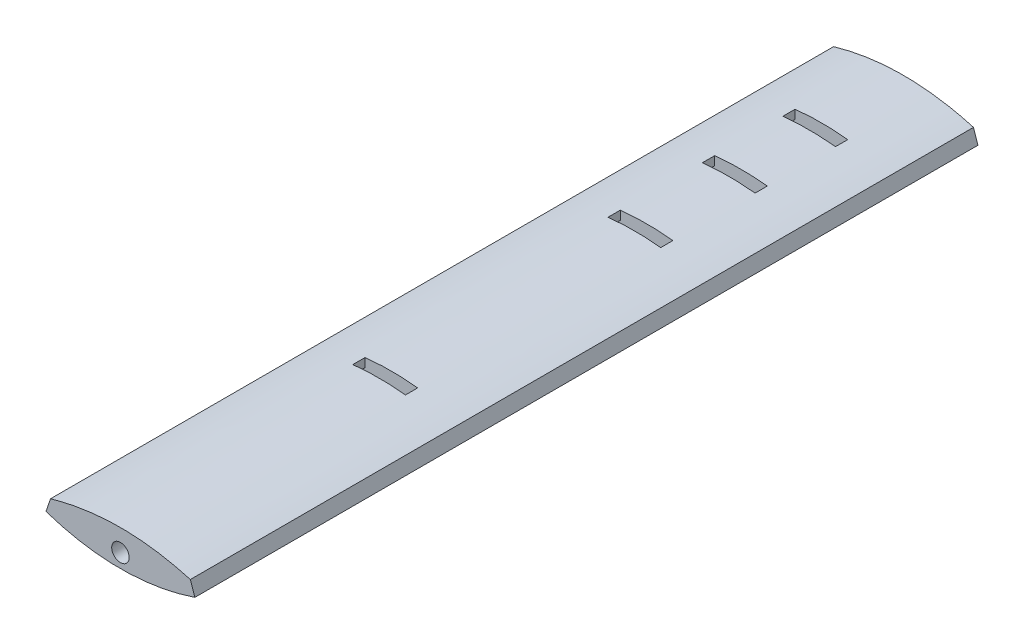
SolidWorks part; units mm, degrees
ref_plane "Front Plane" through (0, 0, 0) normal (0, 0, 1) x (1, 0, 0)
ref_plane "Top Plane" through (0, 0, 0) normal (0, 1, 0) x (1, 0, 0)
ref_plane "Right Plane" through (0, 0, 0) normal (1, 0, 0) x (0, 0, -1)
sketch "Sketch1" plane through (0, 0, 0) normal (0, 0, 1) x (-1, 0, 0)
  line L0 (-10.6452, 31.2359) -> (-10, 29.3428)
  line L1 (-10, 29.3428) -> (0, 27.9) construction
  line L3 (0, 27.9) -> (10, 29.3428) construction
  line L4 (10, 29.3428) -> (10.6452, 31.2359)
  circle A0 centre (0, 31) radius 2
  circle A2 centre (0, 31) radius 1.25
  arc A4 (10.6452, 31.2359) -> (-10.6452, 31.2359) centre (0, 0) ccw
  spline S0 degree 2 poles (-10, 29.3428) (0, 26.4572) (10, 29.3428) knots 0 0 0 1 1 1
sketch "Sketch2" plane through (0, 0, 0) normal (0, 0, 1) x (1, 0, 0)
  line L0 (-10, -29.3428) -> (-10.6452, -31.2359) construction
  line L1 (-10, -29.3428) -> (-10.6452, -31.2359)
  line L2 (10.6452, -31.2359) -> (10, -29.3428) construction
  line L3 (10.6452, -31.2359) -> (10, -29.3428)
  arc A0 (-10.6452, -31.2359) -> (10.6452, -31.2359) centre (0, 0) ccw construction
  circle A1 centre (0, -31) radius 1.25 construction
  arc A3 (-10.6452, -31.2359) -> (10.6452, -31.2359) centre (0, 0) ccw
  circle A4 centre (0, -31) radius 1.25
  parabola Q0 (10, -29.3428) -> (-10, -29.3428) focus (0, -45.2274) apex (0, -27.9) construction
  parabola Q1 (10, -29.3428) -> (-10, -29.3428) focus (0, -45.2274) apex (0, -27.9)
extrude "Boss-Extrude1" add sketch "Sketch2" along normal blind 1.5
sketch "Sketch3" plane through (0, 0, 0) normal (0, 0, -1) x (-1, 0, 0)
  line L0 (-10.6452, -31.2359) -> (-10, -29.3428) construction
  line L1 (10, -29.3428) -> (10.6452, -31.2359) construction
  line L2 (-10.6452, -31.2359) -> (-10, -29.3428)
  line L3 (10, -29.3428) -> (10.6452, -31.2359)
  line L4 (0, -31) -> (0, -27.9) construction
  arc A2 (-10.6452, -31.2359) -> (10.6452, -31.2359) centre (0, 0) ccw construction
  arc A3 (-10.6452, -31.2359) -> (-7.7645, -32.0736) centre (0, 0) ccw
  arc A4 (7.7645, -32.0736) -> (10.6452, -31.2359) centre (0, 0) ccw
  parabola Q0 (-10, -29.3428) -> (10, -29.3428) focus (0, -45.2274) apex (0, -27.9) construction
  parabola Q1 (-10, -29.3428) -> (10, -29.3428) focus (0, -45.2274) apex (0, -27.9)
  spline S0 degree 2 poles (-7.7645, -32.0736) (0, -24.9991) (7.7645, -32.0736) knots 0 0 0 1 1 1
  point P12 (-7.7645, -32.0736)
  point P13 (7.7645, -32.0736)
  dimension "D1" = 3
  dimension "D2" = 3
extrude "Boss-Extrude2" add sketch "Sketch3" along normal blind 113.5
ref_plane "Plane1" through (0, 0, -110) normal (0, 0, 1) x (1, 0, 0)
ref_plane "Plane2" through (0, 0, -37) normal (0, 0, 1) x (1, 0, 0)
sketch "Sketch5" plane through (0, 0, -110) normal (0, 0, 1) x (1, 0, 0)
  line L0 (-10, -29.3428) -> (-10.6452, -31.2359) construction
  line L1 (10.6452, -31.2359) -> (10, -29.3428) construction
  line L2 (-10, -29.3428) -> (-10.6452, -31.2359)
  line L3 (10.6452, -31.2359) -> (10, -29.3428)
  arc A0 (-10.6452, -31.2359) -> (10.6452, -31.2359) centre (0, 0) ccw construction
  circle A1 centre (0, -31) radius 1.25 construction
  arc A2 (-10.6452, -31.2359) -> (10.6452, -31.2359) centre (0, 0) ccw
  circle A3 centre (0, -31) radius 1.25
  parabola Q0 (10, -29.3428) -> (-10, -29.3428) focus (0, -45.2274) apex (0, -27.9) construction
  parabola Q1 (10, -29.3428) -> (-10, -29.3428) focus (0, -45.2274) apex (0, -27.9)
extrude "Boss-Extrude4" add sketch "Sketch5" against normal up to vertex (3.5 mm away)
sketch "Sketch6" plane through (0, 0, -37) normal (0, 0, 1) x (1, 0, 0)
  line L2 (-10, -29.3428) -> (-10.6452, -31.2359)
  line L3 (10.6452, -31.2359) -> (10, -29.3428)
  line L4 (-10, -29.3428) -> (-10.6452, -31.2359)
  line L5 (10.6452, -31.2359) -> (10, -29.3428)
  circle A0 centre (0, -31) radius 1.25 construction
  arc A1 (-10.6452, -31.2359) -> (10.6452, -31.2359) centre (0, 0) ccw
  arc A2 (-10.6452, -31.2359) -> (10.6452, -31.2359) centre (0, 0) ccw
  circle A3 centre (0, -31) radius 1.25
  parabola Q1 (10, -29.3428) -> (-10, -29.3428) focus (0, -45.2274) apex (0, -27.9)
  parabola Q2 (10, -29.3428) -> (-10, -29.3428) focus (0, -45.2274) apex (0, -27.9)
  dimension "D1" = 0
extrude "Boss-Extrude5" add sketch "Sketch6" along normal blind 1.5
ref_plane "Plane4" through (0, 0, -73.5) normal (0, 0, 1) x (1, 0, 0)
sketch "Sketch8" plane through (0, 0, -73.5) normal (0, 0, 1) x (1, 0, 0)
  line L2 (-10, -29.3428) -> (-10.6452, -31.2359)
  line L3 (10.6452, -31.2359) -> (10, -29.3428)
  line L4 (-10, -29.3428) -> (-10.6452, -31.2359)
  line L5 (10.6452, -31.2359) -> (10, -29.3428)
  circle A0 centre (0, -31) radius 1.25 construction
  arc A1 (-10.6452, -31.2359) -> (10.6452, -31.2359) centre (0, 0) ccw
  arc A2 (-10.6452, -31.2359) -> (10.6452, -31.2359) centre (0, 0) ccw
  circle A3 centre (0, -31) radius 1.25
  parabola Q1 (10, -29.3428) -> (-10, -29.3428) focus (0, -45.2274) apex (0, -27.9)
  parabola Q2 (10, -29.3428) -> (-10, -29.3428) focus (0, -45.2274) apex (0, -27.9)
  dimension "D1" = 0
extrude "Boss-Extrude7" add sketch "Sketch8" along normal blind 1.5
ref_plane "Plane5" through (0, 0, -76.75) normal (0, 0, 1) x (1, 0, 0)
sketch "Sketch9" plane through (0, 0, -76.75) normal (0, 0, 1) x (1, 0, 0)
  line L2 (-10, -29.3428) -> (-10.6452, -31.2359)
  line L3 (10.6452, -31.2359) -> (10, -29.3428)
  line L4 (-10, -29.3428) -> (-10.6452, -31.2359)
  line L5 (10.6452, -31.2359) -> (10, -29.3428)
  circle A0 centre (0, -31) radius 1.25 construction
  arc A1 (-10.6452, -31.2359) -> (10.6452, -31.2359) centre (0, 0) ccw
  arc A2 (-10.6452, -31.2359) -> (10.6452, -31.2359) centre (0, 0) ccw
  circle A3 centre (0, -31) radius 1.25
  parabola Q1 (10, -29.3428) -> (-10, -29.3428) focus (0, -45.2274) apex (0, -27.9)
  parabola Q2 (10, -29.3428) -> (-10, -29.3428) focus (0, -45.2274) apex (0, -27.9)
  dimension "D1" = 0
extrude "Boss-Extrude8" add sketch "Sketch9" along normal blind 1.5
ref_plane "Plane6" through (0, 0, -40.25) normal (0, 0, 1) x (1, 0, 0)
sketch "Sketch10" plane through (0, 0, -40.25) normal (0, 0, 1) x (1, 0, 0)
  line L2 (-10, -29.3428) -> (-10.6452, -31.2359)
  line L3 (10.6452, -31.2359) -> (10, -29.3428)
  line L4 (-10, -29.3428) -> (-10.6452, -31.2359)
  line L5 (10.6452, -31.2359) -> (10, -29.3428)
  circle A0 centre (0, -31) radius 1.25 construction
  arc A1 (-10.6452, -31.2359) -> (10.6452, -31.2359) centre (0, 0) ccw
  arc A2 (-10.6452, -31.2359) -> (10.6452, -31.2359) centre (0, 0) ccw
  circle A3 centre (0, -31) radius 1.25
  parabola Q1 (10, -29.3428) -> (-10, -29.3428) focus (0, -45.2274) apex (0, -27.9)
  parabola Q2 (10, -29.3428) -> (-10, -29.3428) focus (0, -45.2274) apex (0, -27.9)
  dimension "D1" = 0
extrude "Boss-Extrude9" add sketch "Sketch10" along normal blind 1.5
ref_plane "Plane7" through (0, 0, -87) normal (0, 0, 1) x (1, 0, 0)
ref_plane "Plane8" through (0, 0, -98.5) normal (0, 0, 1) x (1, 0, 0)
ref_plane "Plane9" through (0, 0, -90.25) normal (0, 0, 1) x (1, 0, 0)
ref_plane "Plane10" through (0, 0, -101.75) normal (0, 0, 1) x (1, 0, 0)
sketch "Sketch12" plane through (0, 0, -101.75) normal (0, 0, 1) x (1, 0, 0)
  line L2 (-10, -29.3428) -> (-10.6452, -31.2359)
  line L3 (10.6452, -31.2359) -> (10, -29.3428)
  line L4 (-10, -29.3428) -> (-10.6452, -31.2359)
  line L5 (10.6452, -31.2359) -> (10, -29.3428)
  circle A0 centre (0, -31) radius 1.25 construction
  arc A1 (-10.6452, -31.2359) -> (10.6452, -31.2359) centre (0, 0) ccw
  arc A2 (-10.6452, -31.2359) -> (10.6452, -31.2359) centre (0, 0) ccw
  circle A3 centre (0, -31) radius 1.25
  parabola Q1 (10, -29.3428) -> (-10, -29.3428) focus (0, -45.2274) apex (0, -27.9)
  parabola Q2 (10, -29.3428) -> (-10, -29.3428) focus (0, -45.2274) apex (0, -27.9)
  dimension "D1" = 0
extrude "Boss-Extrude10" add sketch "Sketch12" along normal blind 1.5
sketch "Sketch13" plane through (0, 0, -90.25) normal (0, 0, 1) x (1, 0, 0)
  line L2 (-10, -29.3428) -> (-10.6452, -31.2359)
  line L3 (10.6452, -31.2359) -> (10, -29.3428)
  line L4 (-10, -29.3428) -> (-10.6452, -31.2359)
  line L5 (10.6452, -31.2359) -> (10, -29.3428)
  circle A0 centre (0, -31) radius 1.25 construction
  arc A1 (-10.6452, -31.2359) -> (10.6452, -31.2359) centre (0, 0) ccw
  arc A2 (-10.6452, -31.2359) -> (10.6452, -31.2359) centre (0, 0) ccw
  circle A3 centre (0, -31) radius 1.25
  parabola Q1 (10, -29.3428) -> (-10, -29.3428) focus (0, -45.2274) apex (0, -27.9)
  parabola Q2 (10, -29.3428) -> (-10, -29.3428) focus (0, -45.2274) apex (0, -27.9)
  dimension "D1" = 0
sketch "Sketch14" plane through (0, 0, -98.5) normal (0, 0, 1) x (1, 0, 0)
  line L2 (-10, -29.3428) -> (-10.6452, -31.2359)
  line L3 (10.6452, -31.2359) -> (10, -29.3428)
  line L4 (-10, -29.3428) -> (-10.6452, -31.2359)
  line L5 (10.6452, -31.2359) -> (10, -29.3428)
  circle A0 centre (0, -31) radius 1.25 construction
  arc A1 (-10.6452, -31.2359) -> (10.6452, -31.2359) centre (0, 0) ccw
  arc A2 (-10.6452, -31.2359) -> (10.6452, -31.2359) centre (0, 0) ccw
  circle A3 centre (0, -31) radius 1.25
  parabola Q1 (10, -29.3428) -> (-10, -29.3428) focus (0, -45.2274) apex (0, -27.9)
  parabola Q2 (10, -29.3428) -> (-10, -29.3428) focus (0, -45.2274) apex (0, -27.9)
  dimension "D1" = 0
sketch "Sketch15" plane through (0, 0, -87) normal (0, 0, 1) x (1, 0, 0)
  line L4 (-10, -29.3428) -> (-10.6452, -31.2359)
  line L5 (10.6452, -31.2359) -> (10, -29.3428)
  line L6 (-10, -29.3428) -> (-10.6452, -31.2359)
  line L7 (10.6452, -31.2359) -> (10, -29.3428)
  circle A1 centre (0, -31) radius 1.25 construction
  arc A2 (-10.6452, -31.2359) -> (10.6452, -31.2359) centre (0, 0) ccw
  arc A3 (-10.6452, -31.2359) -> (10.6452, -31.2359) centre (0, 0) ccw
  circle A4 centre (0, -31) radius 1.25
  parabola Q2 (10, -29.3428) -> (-10, -29.3428) focus (0, -45.2274) apex (0, -27.9)
  parabola Q3 (10, -29.3428) -> (-10, -29.3428) focus (0, -45.2274) apex (0, -27.9)
  dimension "D1" = 0
extrude "Boss-Extrude11" add sketch "Sketch13" along normal blind 1.5
extrude "Boss-Extrude12" add sketch "Sketch14" along normal blind 1.5
extrude "Boss-Extrude13" add sketch "Sketch15" along normal blind 1.5
sketch "Sketch16" plane through (0, 0, 0) normal (0, 1, 0) x (1, 0, 0)
  line L0 (7.7645, 37) -> (-7.7645, 37) construction
  line L1 (-7.7645, 38.75) -> (7.7645, 38.75) construction
  line L2 (-7.7645, 38.75) -> (-7.7645, 37) construction
  line L3 (7.7645, 38.75) -> (7.7645, 37) construction
  line L4 (7.7645, 37) -> (-7.7645, 37) construction
  line L5 (-7.7645, 38.75) -> (7.7645, 38.75) construction
  line L6 (-7.7645, 38.75) -> (-7.7645, 37) construction
  line L7 (7.7645, 38.75) -> (7.7645, 37) construction
  line L8 (-3.7645, 37) -> (-3.7645, 38.75)
  line L9 (3.7645, 37) -> (3.7645, 38.75)
  line L11 (-3.7645, 37) -> (3.7645, 37)
  line L12 (-3.7645, 38.75) -> (3.7645, 38.75)
  dimension "D1" = 4
  dimension "D2" = 4
  dimension "D3" = 7.529
extrude "Cut-Extrude6" cut sketch "Sketch16" against normal through all
pattern_linear "LPattern1" count 2 spacing 36.5 along (0, 0, -1) of "Cut-Extrude6"
pattern_linear "LPattern2" count 2 spacing 50 along (0, 0, -1) of "Cut-Extrude6"
pattern_linear "LPattern3" count 2 spacing 61.5 along (0, 0, -1) of "Cut-Extrude6"
sketch "Sketch17" plane through (0, 0, 1.5) normal (0, 0, 1) x (1, 0, 0)
  circle A0 centre (4.423, -31.3105) radius 32.8718
extrude "Cut-Extrude7" cut sketch "Sketch17" against normal blind 1.5
sketch "Sketch18" plane through (0, 0, -113.5) normal (0, 0, -1) x (-1, 0, 0)
  circle A0 centre (-2.6837, -30.6378) radius 61.2483
extrude "Cut-Extrude8" cut sketch "Sketch18" against normal blind 1.5
sketch "Sketch19" plane through (0, 0, 0) normal (0, 0, 1) x (1, 0, 0)
  line L2 (-10, -29.3428) -> (-10.6452, -31.2359)
  line L3 (10.6452, -31.2359) -> (10, -29.3428)
  line L4 (-10, -29.3428) -> (-10.6452, -31.2359)
  line L5 (10.6452, -31.2359) -> (10, -29.3428)
  circle A0 centre (0, -31) radius 1.25 construction
  arc A1 (-10.6452, -31.2359) -> (10.6452, -31.2359) centre (0, 0) ccw
  arc A2 (-10.6452, -31.2359) -> (10.6452, -31.2359) centre (0, 0) ccw
  circle A3 centre (0, -31) radius 1.25
  parabola Q1 (10, -29.3428) -> (-10, -29.3428) focus (0, -45.2274) apex (0, -27.9)
  parabola Q2 (10, -29.3428) -> (-10, -29.3428) focus (0, -45.2274) apex (0, -27.9)
  dimension "D1" = 0
extrude "Boss-Extrude15" add sketch "Sketch19" against normal blind 2
fillet "Fillet1" radius 0.5 10 edges
